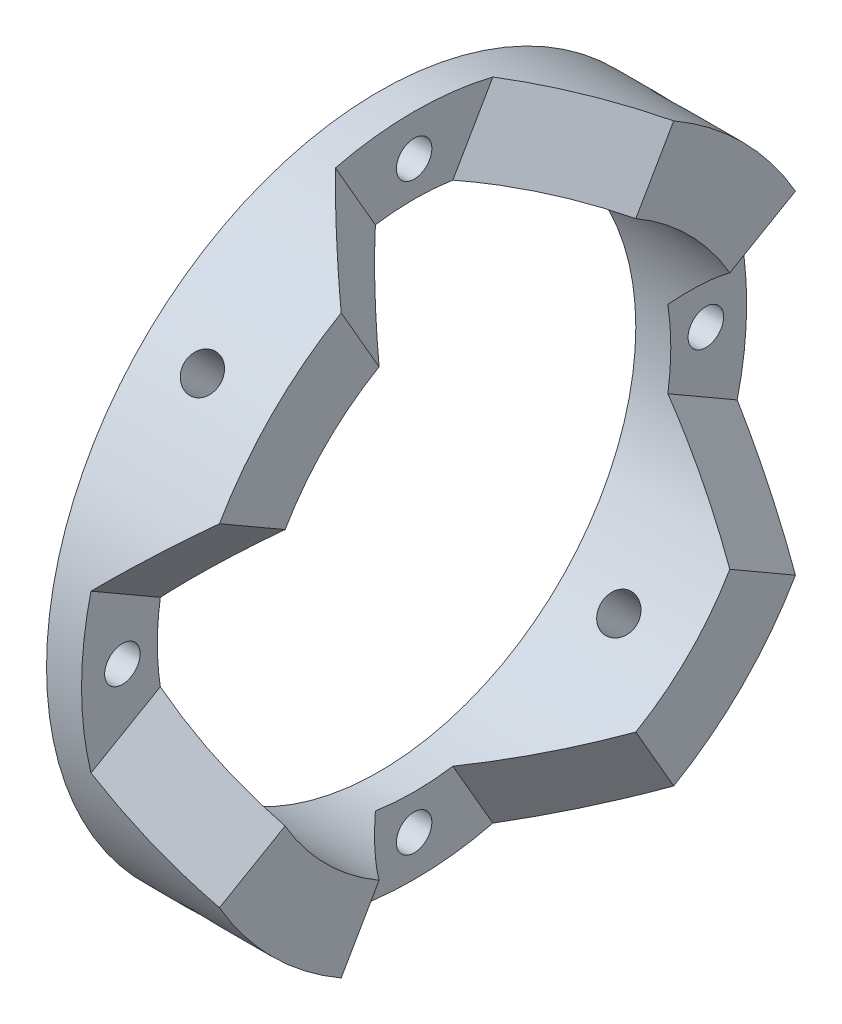
SolidWorks part; units mm, degrees
material "ABS"
ref_plane "Front Plane" through (0, 0, 0) normal (1, 0, 0) x (0, 1, 0)
ref_plane "Top Plane" through (0, 0, 0) normal (0, 0, 1) x (0, 1, 0)
ref_plane "Right Plane" through (0, 0, 0) normal (0, 1, 0) x (-1, 0, 0)
sketch "Sketch1" plane through (0, 0, 0) normal (1, 0, 0) x (0, 1, 0)
  circle A0 centre (0, 0) radius 36.195 construction
  circle A1 centre (0, 0) radius 36.195
  circle A2 centre (0, 0) radius 27.94
  circle A3 centre (0, -31.75) radius 1.9304
  circle A4 centre (-31.75, 0) radius 1.9304
  circle A5 centre (0, 31.75) radius 1.9304
  circle A8 centre (31.75, 0) radius 1.9304
  point P15 (0, 0)
  dimension "D1" = 72.39
  dimension "D2" = 27.94
  dimension "D4" = 3.8608
  dimension "D3" = 31.75
  dimension "D5" = 4
extrude "Boss-Extrude1" add sketch "Sketch1" along normal blind 3.81
sketch "Sketch2" plane through (3.81, 0, 0) normal (1, 0, 0) x (0, 1, 0)
  line L0 (18.0975, 31.3458) -> (13.97, 24.1967)
  line L1 (31.3458, 18.0975) -> (24.1967, 13.97)
  line L2 (18.0975, -31.3458) -> (13.97, -24.1967)
  line L3 (31.3458, -18.0975) -> (24.1967, -13.97)
  line L4 (-31.3458, -18.0975) -> (-24.1967, -13.97)
  line L5 (-18.0975, -31.3458) -> (-13.97, -24.1967)
  line L6 (-18.0975, 31.3458) -> (-13.97, 24.1967)
  line L7 (-31.3458, 18.0975) -> (-24.1967, 13.97)
  arc A0 (24.1967, -13.97) -> (13.97, -24.1967) centre (0, 0) cw
  circle A1 centre (0, 0) radius 36.195 construction
  arc A2 (31.3458, -18.0975) -> (18.0975, -31.3458) centre (0, 0) cw
  arc A3 (-13.97, -24.1967) -> (-24.1967, -13.97) centre (0, 0) cw
  arc A4 (18.0975, 31.3458) -> (31.3458, 18.0975) centre (0, 0) cw
  circle A5 centre (0, 0) radius 27.94 construction
  arc A6 (13.97, 24.1967) -> (24.1967, 13.97) centre (0, 0) cw
  circle A7 centre (0, 0) radius 27.94 construction
  arc A8 (-18.0975, -31.3458) -> (-31.3458, -18.0975) centre (0, 0) cw
  arc A9 (-24.1967, 13.97) -> (-13.97, 24.1967) centre (0, 0) cw
  arc A10 (-31.3458, 18.0975) -> (-18.0975, 31.3458) centre (0, 0) cw
  circle A11 centre (0, 0) radius 36.195 construction
  point P6 (31.5764, 17.6921)
  point P16 (0, 0)
  point P32 (0, 0)
  dimension "D1" = 30
  dimension "D2" = 4
extrude "Boss-Extrude2" add sketch "Sketch2" along normal blind 10.16
ref_plane "Plane1" through (0, 24.7216, 24.7216) normal (0, 0.7071, 0.7071) x (1, 0, 0)
sketch "Sketch4" plane through (0, 24.7216, 24.7216) normal (0, 0.7071, 0.7071) x (1, 0, 0)
  line L0 (0, 36.195) -> (0, -36.195) construction
  circle A0 centre (6.35, 0) radius 1.9685
  point P2 (0, 0)
  point P4 (7.3968, 0)
  dimension "D1" = 3.937
  dimension "D2" = 6.35
extrude "Cut-Extrude1" cut sketch "Sketch4" against normal blind 10.16 and the other way blind 2.54
ref_axis "Axis1" through (14.6685, 0, 0) along (-1, 0, 0)
pattern_circular "CirPattern1" count 4 every 90 about axis through (14.6685, 0, 0) along (-1, 0, 0) of "Cut-Extrude1"
chamfer "Chamfer1" distance 10.16 angle 45 8 edges at (3.81, -16.0337, -27.7713) (3.81, 16.0337, -27.7713) (3.81, 16.0337, 27.7713) (3.81, -16.0337, 27.7713) (3.81, -27.7713, 16.0337) (3.81, -27.7713, -16.0337) (3.81, 27.7713, 16.0337) (3.81, 27.7713, -16.0337)
